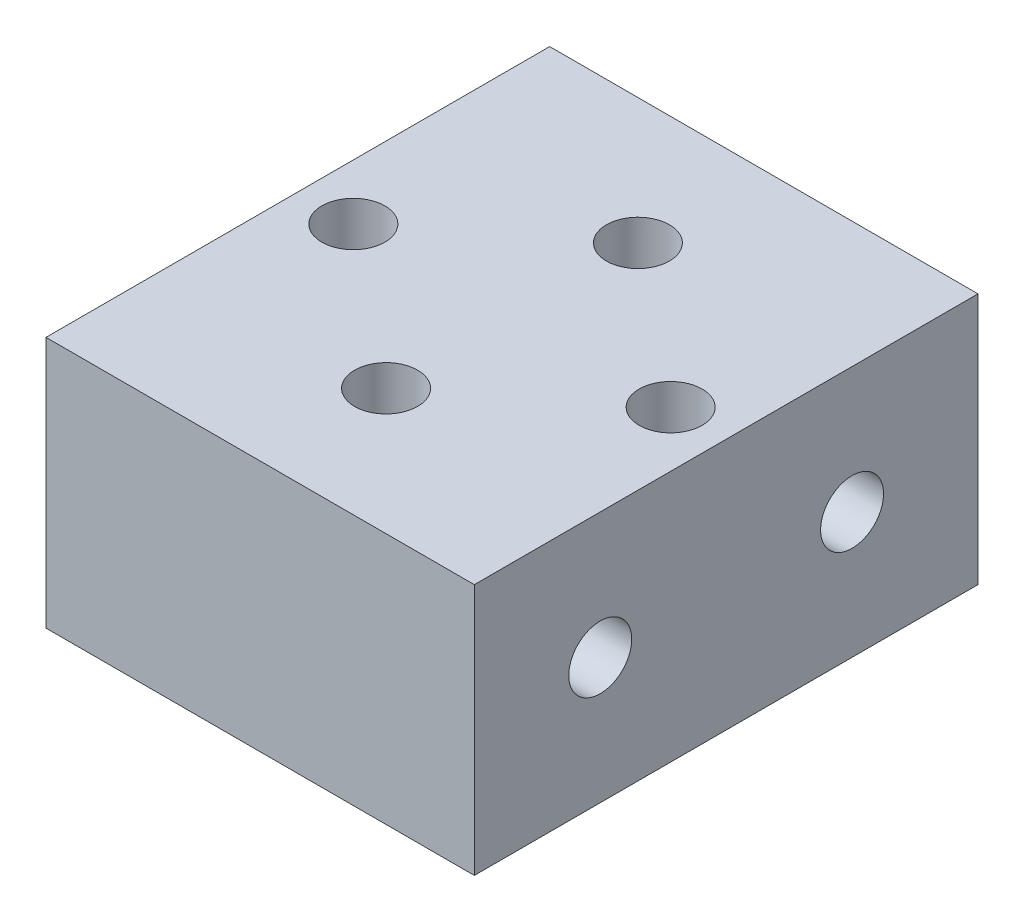
SolidWorks part; units mm, degrees
ref_plane "Front Plane" through (0, 0, 0) normal (0, 0, 1) x (1, 0, 0)
ref_plane "Top Plane" through (0, 0, 0) normal (0, 1, 0) x (1, 0, 0)
ref_plane "Right Plane" through (0, 0, 0) normal (1, 0, 0) x (0, 0, -1)
sketch "Sketch1" plane through (0, 0, 0) normal (0, 1, 0) x (1, 0, 0)
  line L1 (-4.05, -4.7625) -> (4.05, -4.7625)
  line L2 (-4.05, -4.7625) -> (-4.05, 4.7625)
  line L3 (-4.05, 4.7625) -> (4.05, 4.7625)
  line L4 (4.05, -4.7625) -> (4.05, 4.7625)
  line L5 (-4.05, -4.7625) -> (4.05, 4.7625) construction
  line L6 (-4.05, 4.7625) -> (4.05, -4.7625) construction
  point P0 (0, 0)
  dimension "D1" = 8.1
  dimension "D2" = 9.525
extrude "Boss-Extrude1" add sketch "Sketch1" along normal blind 4.7625
hole_wizard "#0-80 Tapped Hole1" positions "Sketch3" profile "Sketch2" tap size "#0-80" standard "Ansi Inch" end condition through all
sketch "Sketch3" plane through (-4.05, 0, 0) normal (-1, 0, 0) x (0, 0, 1)
  line L0 (4.7625, 4.7625) -> (4.7625, 0) construction
  line L1 (-4.7625, 4.7625) -> (-4.7625, 0) construction
  point P0 (-2.3813, 2.3813)
  point P1 (2.3813, 2.3813)
  point P6 (4.7625, 2.3813)
  point P9 (-4.7625, 2.3813)
  dimension "D1" = 2.3813
  dimension "D2" = 2.3813
sketch "Sketch2" plane through (-4.05, 2.3813, -2.3813) normal (0, 1, 0) x (0, 0, 1)
  line L0 (0, 0) -> (0, 8.1)
  line L1 (0, 8.1) -> (0.5956, 8.1)
  line L2 (0.5956, 8.1) -> (0.5956, 0)
  line L5 (0.5956, 0) -> (0, 0)
  line L11 (0, -6.35) -> (0, 107.95) construction
  dimension "Thread Major Dia." = 1.1913
  dimension "Thru Tap Drill Depth" = 8.1
hole_wizard "#0-80 Tapped Hole2" positions "Sketch5" profile "Sketch4" tap size "#0-80" standard "Ansi Inch" end condition through all
sketch "Sketch5" plane through (0, 0, 0) normal (0, -1, 0) x (1, 0, 0)
  line L0 (-4.05, -4.7625) -> (-4.05, 4.7625) construction
  point P0 (-3, 0)
  point P1 (3, 0)
  point P6 (-4.05, 0)
  dimension "D1" = 3
  dimension "D2" = 3
sketch "Sketch4" plane through (-3, 0, 0) normal (1, 0, 0) x (0, 0, -1)
  line L0 (0, 0) -> (0, 4.7625)
  line L1 (0, 4.7625) -> (0.5956, 4.7625)
  line L2 (0.5956, 4.7625) -> (0.5956, 0)
  line L5 (0.5956, 0) -> (0, 0)
  line L11 (0, -6.35) -> (0, 107.95) construction
  dimension "Thread Major Dia." = 1.1913
  dimension "Thru Tap Drill Depth" = 4.7625
hole_wizard "3/64 (0.04688) Diameter Hole1" positions "Sketch7" profile "Sketch6" hole size "3/64" standard "Ansi Inch"
sketch "Sketch7" plane through (0, 4.7625, 0) normal (0, 1, 0) x (-1, 0, 0)
  line L0 (4.05, 4.7625) -> (-4.05, 4.7625) construction
  line L5 (-4.05, -4.7625) -> (4.05, -4.7625) construction
  point P1 (0, 2.3813)
  point P3 (0, -2.3813)
  point P9 (0, 4.7625)
  dimension "D1" = 2.3813
  dimension "D2" = 2.3813
sketch "Sketch6" plane through (0, 4.7625, 2.3813) normal (1, 0, 0) x (0, 0, 1)
  line L0 (0, 0) -> (0, 13.3117)
  line L1 (0, 13.3117) -> (0.5954, 12.954)
  line L2 (0.5954, 12.954) -> (0.5954, 0)
  line L5 (0.5954, 0) -> (0, 0)
  line L10 (0, 13.3117) -> (-0.5954, 12.954) construction
  line L11 (0, -6.35) -> (0, 107.95) construction
  dimension "Hole Dia." = 1.1908
  dimension "Hole Depth" = 12.954
  dimension "Drill Angle" = 118
